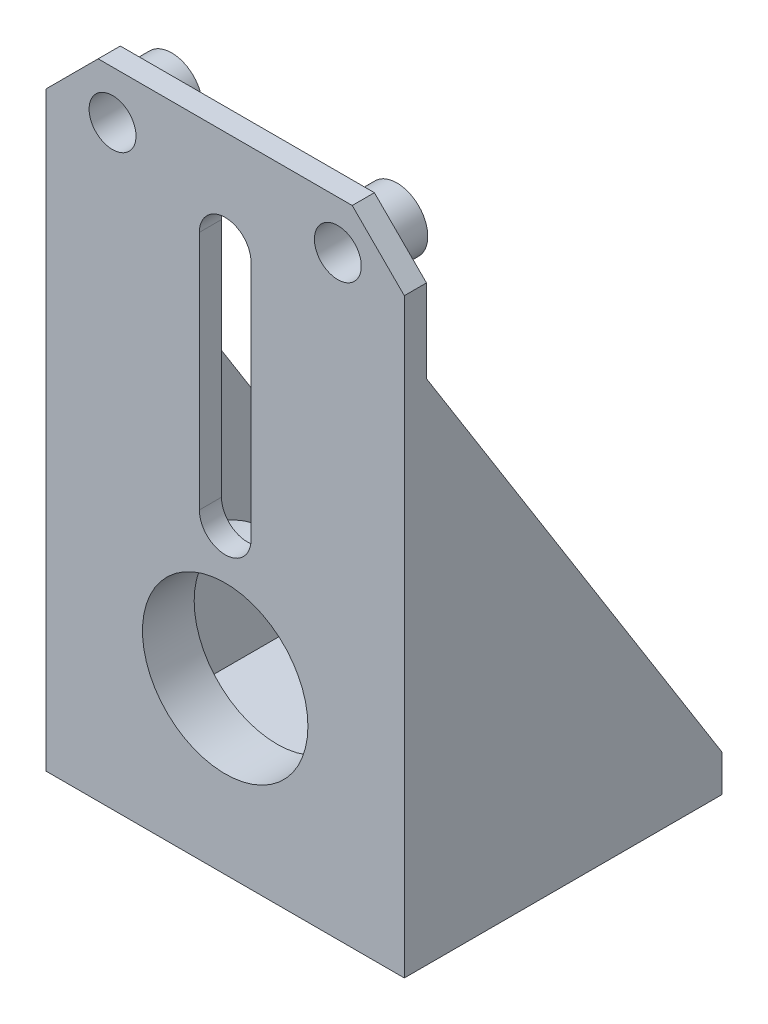
SolidWorks part; units mm, degrees
ref_plane "Front Plane" through (0, 0, 0) normal (0, 0, 1) x (1, 0, 0)
ref_plane "Top Plane" through (0, 0, 0) normal (0, 1, 0) x (1, 0, 0)
ref_plane "Right Plane" through (0, 0, 0) normal (1, 0, 0) x (0, 0, -1)
sketch "Sketch1" plane through (0, 0, 0) normal (0, 0, 1) x (1, 0, 0)
  line L0 (-33.4213, -6) -> (-33.4213, 36.5)
  line L2 (9.0787, 36.5) -> (9.0787, -6)
  line L3 (9.0787, -6) -> (-33.4213, -6)
  line L5 (-33.4213, 36.5) -> (9.0787, 36.5) construction
  line L7 (-28.4213, 77.55) -> (4.0787, 77.55)
  line L10 (-33.4213, 36.5) -> (-33.4213, 72.55)
  line L11 (-33.4213, 72.55) -> (-28.4213, 77.55)
  line L12 (-12.1713, 36.5) -> (-12.1713, 77.55) construction
  line L13 (9.0787, 36.5) -> (9.0787, 72.55)
  line L14 (9.0787, 72.55) -> (4.0787, 77.55)
  circle A0 centre (2.9277, 30.5) radius 1.55
  circle A1 centre (2.9277, -0.5) radius 1.5
  circle A2 centre (-27.6713, -0.5) radius 1.5
  circle A3 centre (-28.0723, 30.5) radius 1.5
  circle A4 centre (-12.1713, 15.25) radius 11
  circle A5 centre (-27.4213, 71.55) radius 3.175
  circle A6 centre (3.0787, 71.55) radius 3.175
  dimension "D5" = 22
  dimension "D10" = 3.1
  dimension "D13" = 6
  dimension "D16" = 6.35
  dimension "D1" = 42.5
  dimension "D2" = 42.5
  dimension "D3" = 31
  dimension "D4" = 31
  dimension "D6" = 62.3
  dimension "D7" = 21.25
  dimension "D8" = 21.25
  dimension "D9" = 5
  dimension "D11" = 5.5
  dimension "D12" = 5.5
  dimension "D14" = 6
  dimension "D15" = 6
extrude "Boss-Extrude1" add sketch "Sketch1" along normal blind 3
sketch "Sketch2" plane through (0, 0, 0) normal (0, 0, -1) x (-1, 0, 0)
  circle A0 centre (-3.0787, 71.55) radius 3.175
  circle A1 centre (27.4213, 71.55) radius 3.175
  circle A2 centre (-3.0787, 71.55) radius 4.175
  circle A3 centre (27.4213, 71.55) radius 4.175
  dimension "D1" = 6.35
  dimension "D2" = 6.35
  dimension "D3" = 1
  dimension "1" = 1
extrude "Boss-Extrude2" add sketch "Sketch2" along normal blind 3
sketch "Sketch3" plane through (0, 0, -3) normal (0, 0, -1) x (-1, 0, 0)
  circle A0 centre (-3.0787, 71.55) radius 4.175
  circle A1 centre (27.4213, 71.55) radius 4.175
  dimension "D1" = 8.35
  dimension "D2" = 8.35
extrude "Boss-Extrude3" add sketch "Sketch3" along normal blind 2
sketch "Sketch4" plane through (0, 0, 0) normal (0, 0, -1) x (-1, 0, 0)
  line L0 (33.4213, -6) -> (-9.0787, -6)
  line L2 (-9.0787, -9) -> (33.259, -9)
  line L4 (-9.0787, -4) -> (-12.0787, -4)
  line L5 (-9.0787, -6) -> (-9.0787, 72.55) construction
  line L6 (-12.0787, -4) -> (-12.0787, -9)
  line L7 (-12.0787, -9) -> (-9.0787, -9)
  line L8 (-9.0787, -6) -> (-9.0787, -4)
  line L10 (36.259, -9) -> (33.259, -9)
  line L11 (36.259, -4) -> (36.259, -9)
  line L12 (33.259, -4) -> (36.259, -4)
  line L13 (33.4213, -6) -> (33.259, -4)
  dimension "D1" = 3
  dimension "D2" = 3
  dimension "D3" = 5
  dimension "D4" = 3
  dimension "5" = 5
  dimension "D5" = 3
extrude "Boss-Extrude4" add sketch "Sketch4" along normal blind 40 and the other way blind 3 separate body
sketch "Sketch5" plane through (0, 0, 3) normal (0, 0, 1) x (1, 0, 0)
  line L1 (9.0787, 48.0314) -> (9.0787, 43.0314)
  line L2 (9.0787, -6) -> (9.0787, 72.55) construction
  line L3 (9.0787, 48.0314) -> (12.0787, 48.0314)
  line L4 (12.0787, 48.0314) -> (12.0787, 43.0314)
  line L5 (12.0787, 43.0314) -> (9.0787, 43.0314)
  line L6 (-33.4213, 45.5314) -> (9.0787, 45.5314) construction
  line L11 (-12.1713, 45.5314) -> (-12.1713, 51.3356) construction
  line L12 (-36.4213, 48.0314) -> (-36.4213, 43.0314)
  line L16 (-33.4213, 48.0314) -> (-36.4213, 48.0314)
  line L17 (-33.4213, 48.0314) -> (-33.4213, 43.0314)
  line L18 (-36.4213, 43.0314) -> (-33.4213, 43.0314)
  circle A0 centre (2.9277, 30.5) radius 1.55 construction
  dimension "D2" = 12.5314
  dimension "D1" = 3
  dimension "D3" = 3
  dimension "D4" = 5
  dimension "D5" = 3
  dimension "D6" = 42.5
extrude "Boss-Extrude5" add sketch "Sketch5" against normal blind 3
sketch "Sketch6" plane through (9.0787, 0, 0) normal (1, 0, 0) x (0, 0, -1)
  line L0 (0, 48.0314) -> (40, -4)
  line L1 (0, 43.0314) -> (36.1562, -4)
  line L2 (0, 48.0314) -> (0, 43.0314)
  line L3 (36.1562, -4) -> (40, -4)
  line L4 (-3, -4) -> (40, -4) construction
extrude "Boss-Extrude7" add sketch "Sketch6" along normal blind 3
sketch "Sketch8" plane through (-36.4213, 0, 0) normal (-1, 0, 0) x (0, 0, 1)
  line L0 (0, 48.0314) -> (0, 43.0314)
  line L1 (0, 43.0314) -> (-36.1562, -4)
  line L2 (-36.1562, -4) -> (-40, -4)
  line L3 (-40, -4) -> (0, 48.0314)
extrude "Boss-Extrude9" add sketch "Sketch8" against normal blind 3
sketch "Sketch9" plane through (0, 0, 3) normal (0, 0, 1) x (1, 0, 0)
  circle A0 centre (2.9277, 30.5) radius 1.55
  circle A1 centre (-28.0723, 30.5) radius 1.5
  circle A2 centre (-27.6713, -0.5) radius 1.5
  circle A3 centre (2.9277, -0.5) radius 1.5
  circle A4 centre (-12.1713, 15.25) radius 11
extrude "Boss-Extrude10" add sketch "Sketch9" against normal blind 3
sketch "Sketch10" plane through (0, 0, 3) normal (0, 0, 1) x (1, 0, 0)
  line L0 (-33.4213, 14) -> (9.0787, 14) construction
  line L1 (-33.4213, -4) -> (-33.4213, 43.0314) construction
  line L2 (9.0787, 43.0314) -> (9.0787, -4) construction
  line L3 (12.0787, -9) -> (-36.259, -9) construction
  line L4 (-12.1713, 14) -> (-12.1713, 31.04) construction
  line L5 (-33.4213, 43.0314) -> (-33.4213, -4) construction
  circle A0 centre (-12.1713, 14) radius 11.2
  dimension "D3" = 22.4
  dimension "D1" = 23
  dimension "D2" = 21.25
extrude "Cut-Extrude1" cut sketch "Sketch10" against normal blind 22.7
sketch "Sketch11" plane through (0, 0, 3) normal (0, 0, 1) x (1, 0, 0)
  line L0 (-12.1713, 25.2) -> (-12.1713, 67.2554) construction
  line L1 (-12.1713, 64.55) -> (-12.1713, 32) construction
  line L2 (-8.6713, 64.55) -> (-8.6713, 32)
  line L3 (-15.6713, 64.55) -> (-15.6713, 32)
  circle A0 centre (-12.1713, 14) radius 11.2 construction
  arc A1 (-8.6713, 64.55) -> (-15.6713, 64.55) centre (-12.1713, 64.55) ccw
  arc A2 (-15.6713, 32) -> (-8.6713, 32) centre (-12.1713, 32) ccw
  circle A3 centre (3.0787, 71.55) radius 3.175 construction
  point P7 (-12.1713, 48.275)
  dimension "D2" = 7
  dimension "D1" = 18
  dimension "D3" = 7
extrude "Cut-Extrude2" cut sketch "Sketch11" against normal blind 10
sketch "Sketch12" plane through (0, 0, 0) normal (0, 0, -1) x (-1, 0, 0)
  circle A0 centre (12.1713, 14) radius 11.2
  circle A1 centre (12.1713, 14) radius 13.5
  dimension "D1" = 22.4
extrude "Boss-Extrude11" add sketch "Sketch12" along normal blind 4
sketch "Sketch13" plane through (0, 0, 3) normal (0, 0, 1) x (1, 0, 0)
  line L0 (-33.4213, 72.55) -> (-36.4213, 72.55)
  line L1 (-36.4213, 72.55) -> (-36.4213, -4)
  line L2 (-36.4213, -4) -> (-33.4213, -4)
  line L3 (-33.4213, -4) -> (-33.4213, 72.55)
  line L7 (12.0787, -4) -> (9.0787, -4)
  line L8 (12.0787, 72.5556) -> (12.0787, -4)
  line L9 (9.0787, 72.55) -> (12.0787, 72.5556)
  line L10 (9.0787, -4) -> (9.0787, 72.55)
extrude "Boss-Extrude13" add sketch "Sketch13" against normal blind 3
sketch "Sketch14" plane through (12.0787, 0, 0) normal (1, 0, 0) x (0, 0, -1)
  line L0 (-3, 64.55) -> (-3, -9)
  line L1 (-3, 72.5556) -> (-3, -9) construction
  line L3 (-3, -9) -> (40, -9) construction
  line L4 (-3, -9) -> (40, -9)
  line L5 (40, -9) -> (40, -4)
  line L6 (40, -4) -> (-3, 64.55)
extrude "Boss-Extrude14" add sketch "Sketch14" against normal blind 3
sketch "Sketch15" plane through (-36.4213, 0, 0) normal (-1, 0, 0) x (0, 0, 1)
  line L0 (3, 64.55) -> (-40, -4)
  line L1 (-40, -4) -> (-40, -9)
  line L2 (3, -9) -> (-40, -9) construction
  line L3 (-40, -9) -> (-40, -4) construction
  line L4 (-40, -9) -> (3, -9)
  line L5 (3, -9) -> (3, 64.55)
  dimension "D1" = 73.55
extrude "Boss-Extrude15" add sketch "Sketch15" against normal blind 3
sketch "Sketch16" plane through (0, -4, 0) normal (0, 1, 0) x (1, 0, 0)
  line L0 (-33.4213, 40) -> (-32.9242, 40)
  line L1 (-32.9242, 40) -> (-32.9242, 0)
  line L2 (-33.4213, 0) -> (9.0787, 0) construction
  line L3 (-32.9242, 0) -> (-33.4213, 0)
  line L4 (-33.4213, 0) -> (-33.4213, 40)
extrude "Cut-Extrude3" cut sketch "Sketch16" against normal blind 2
chamfer "Chamfer1" distance 3 angle 45 2 edges at (-36.4213, 72.55, 1.5) (12.0787, 72.5556, 1.5) first distance on face at (-36.4213, 30.4779, -12.3333) first distance on face at (10.5787, 72.5528, 1.5)
sketch "Sketch17" plane through (0, 0, 3) normal (0, 0, 1) x (1, 0, 0)
  line L0 (-28.4213, 77.55) -> (-36.4213, 69.55)
  line L2 (-36.4213, 70.9996) -> (-29.3709, 78.05)
  line L3 (-29.3709, 78.05) -> (5.0283, 78.05)
  line L4 (-12.1713, 78.05) -> (-12.1713, 77.55)
  line L5 (4.0787, 77.55) -> (-28.4213, 77.55) construction
  line L6 (4.0787, 77.55) -> (-28.4213, 77.55)
  line L7 (-12.1713, 77.55) -> (-12.1713, 81.2797) construction
  line L8 (4.0787, 77.55) -> (12.0787, 69.55)
  line L9 (12.0787, 70.9996) -> (5.0283, 78.05)
  line L10 (-36.4213, 69.55) -> (-36.4213, 70.9996)
  line L11 (12.0787, 69.55) -> (12.0787, 70.9996)
  line M9 (-28.4213, 77.55) -> (-33.4213, 72.55)
  line M10 (-33.4213, 72.55) -> (-36.4213, 69.55)
  line M14 (12.0787, 69.5612) -> (9.0787, 72.55)
  line M15 (9.0787, 72.55) -> (4.0787, 77.55)
  line M16 (4.0787, 77.55) -> (-28.4213, 77.55)
  dimension "D1" = 0.5
extrude "Boss-Extrude17" add sketch "Sketch17" against normal blind 3 contours L10 L4 L3 L2 M10 M9 M16 | L11 L9 L3 L4 M14 M16 M15 region at (-31.103, 75.2317, 3) region at (-11.9144, 77.8, 3)
